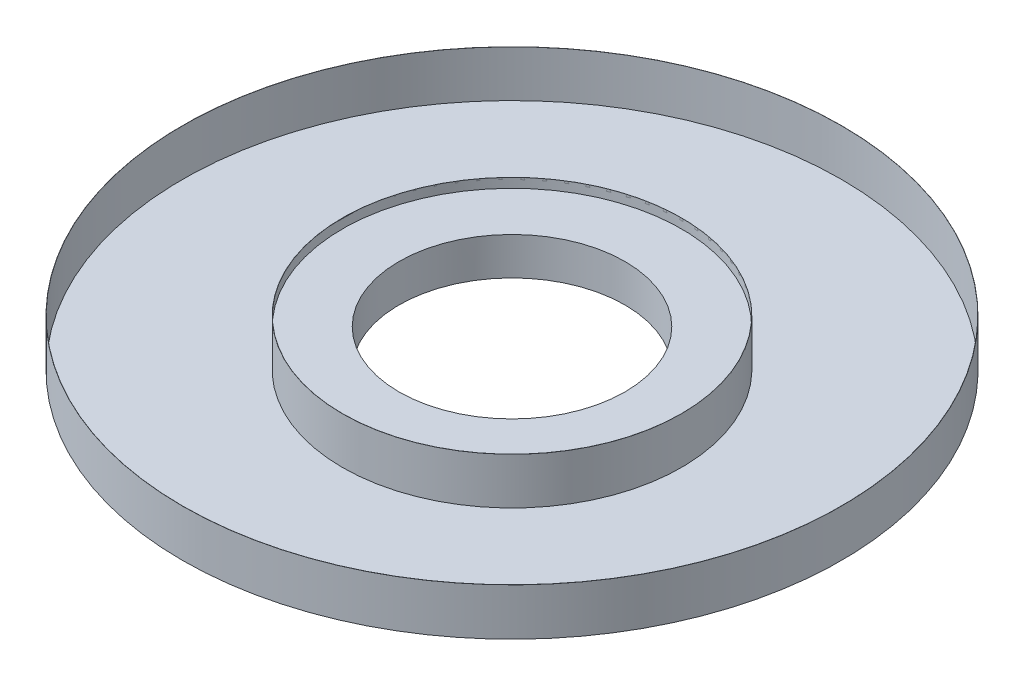
SolidWorks part; units mm, degrees
material "1345 Alloy"
ref_plane "Front Plane" through (0, 0, 0) normal (0, 0, 1) x (1, 0, 0)
ref_plane "Top Plane" through (0, 0, 0) normal (0, 1, 0) x (1, 0, 0)
ref_plane "Right Plane" through (0, 0, 0) normal (1, 0, 0) x (0, 0, -1)
sketch "Sketch1" plane through (0, 0, 0) normal (0, 1, 0) x (1, 0, 0)
  circle A0 centre (0, 0) radius 1750
extrude "Boss-Extrude1" add sketch "Sketch1" along normal blind 500
sketch "Sketch2" plane through (0, 500, 0) normal (0, 1, 0) x (1, 0, 0)
  circle A0 centre (0, 0) radius 900
extrude "Cut-Extrude2" cut sketch "Sketch2" against normal blind 300
sketch "Sketch3" plane through (0, 0, 0) normal (0, -1, 0) x (1, 0, 0)
  circle A0 centre (0, 0) radius 600
extrude "Cut-Extrude3" cut sketch "Sketch3" against normal blind 300
sketch "Sketch4" plane through (0, 500, 0) normal (0, 1, 0) x (1, 0, 0)
  circle A0 centre (0, 0) radius 1749.25
  circle A1 centre (0, 0) radius 900.75
extrude "Cut-Extrude4" cut sketch "Sketch4" against normal blind 497
sketch "Sketch6" plane through (0, 0, 0) normal (1, 0, 0) x (0, 0, -1)
  line L0 (0, 0) -> (0, 250)
  line L1 (0, 250) -> (1750, 250)
  line L2 (1750, 0) -> (1750, 500) construction
  line L3 (1750, 250) -> (1750, 0)
  line L4 (1750, 0) -> (-1750, 0)
  line L5 (-1750, 0) -> (-1750, 250)
  line L6 (-1750, 500) -> (-1750, 0) construction
  line L7 (-1750, 250) -> (0, 250)
  line L8 (1750, 250) -> (1750, 500)
  line L9 (1750, 500) -> (-1750, 500)
  line L10 (-1750, 500) -> (-1750, 250)
extrude "Cut-Extrude5" cut sketch "Sketch6" against normal through all both and the other way through all contours L9 L10 L7 L1 L8 region at (0, 375, 0)
